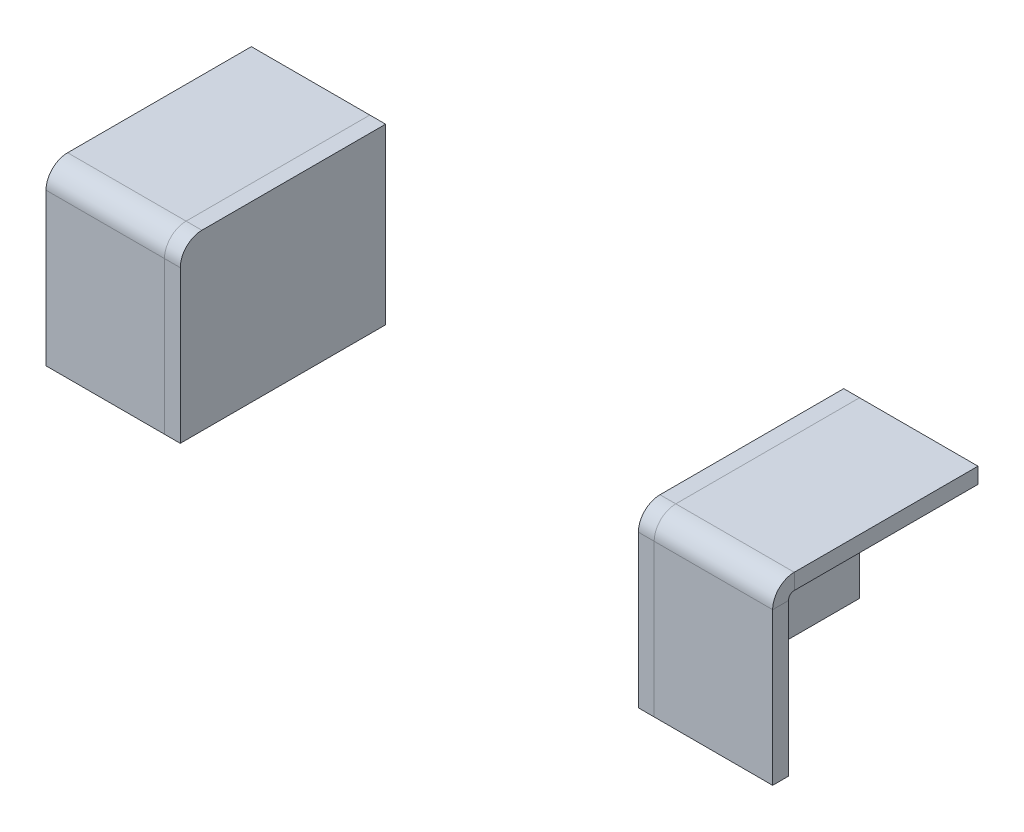
SolidWorks part; units mm, degrees
note: The reader was unsure of these and kept them because the rebuilt part matched: flange length of "Edge-Flange1".
ref_plane "Front Plane" through (0, 0, 0) normal (0, 0, 1) x (1, 0, 0)
ref_plane "Top Plane" through (0, 0, 0) normal (0, 1, 0) x (1, 0, 0)
ref_plane "Right Plane" through (0, 0, 0) normal (1, 0, 0) x (0, 0, -1)
sketch "Sketch1" plane through (0, 0, 0) normal (0, 1, 0) x (1, 0, 0)
  line L1 (-7.5, -13) -> (7.5, -13)
  line L2 (-7.5, -13) -> (-7.5, 13)
  line L3 (-7.5, 13) -> (7.5, 13)
  line L4 (7.5, -13) -> (7.5, 13)
  line L5 (-7.5, -13) -> (7.5, 13) construction
  line L6 (-7.5, 13) -> (7.5, -13) construction
  point P0 (0, 0)
  dimension "D1" = 26
  dimension "D2" = 15
base flange "Base-Flange1" sketch "Sketch1" thickness 2 reverse thickness direction no parameters "D1"=0.7366
edge flange "Edge-Flange1" sketch "Sketch8" flange angle 90 flange length 20 flange position material inside bend radius 0.7366 thickness 2 relief rectangular parameters "D6"=10
sketch "Sketch8" plane through (0, -2, 13) normal (0, 0, 1) x (-1, 0, 0)
  line L0 (7.5, 0) -> (-7.5, 0) construction
  line L1 (7.5, 0) -> (-7.5, 0)
  line L2 (-7.5, 0) -> (-7.5, 20)
  line L3 (-7.5, 20) -> (7.5, 20)
  line L4 (7.5, 20) -> (7.5, 0)
bend "EdgeBend1" bend radius 0.7366 bend angle 90 parameters "D5"=1
sketch "Sketch9" plane through (7.5, 0, 0) normal (1, 0, 0) x (0, 0, -1)
  line L0 (-13, -22) -> (-13, -2.7366) construction
  line L1 (-10.2634, 0) -> (13, 0) construction
  line L2 (-13, -22) -> (-13, -2.7366)
  line L3 (-10.2634, 0) -> (13, 0)
  line L4 (-13, -22) -> (13, -22)
  line L5 (13, -22) -> (13, 0)
  arc A0 (-10.2634, 0) -> (-13, -2.7366) centre (-10.2634, -2.7366) ccw construction
  arc A1 (-10.2634, 0) -> (-13, -2.7366) centre (-10.2634, -2.7366) ccw
base flange "Base-Flange2" sketch "Sketch9" thickness 2 reverse thickness direction yes parameters "D1"=0.7366
ref_plane "Plane1" through (38.5, 0, 0) normal (-1, 0, 0) x (0, 0, 1)
mirror "Mirror1" about plane through (38.5, 0, 0) normal (-1, 0, 0) of bodies 102 103
bend "DerivedBend1" bend radius 0.7366 bend angle 90 parameters "D5"=1
sketch "Bend-Lines1" [suppressed] plane through (0, 0, 0) normal (0, 1, 0) x (1, 0, 0)
sketch "Bounding-Box1" [suppressed] plane through (0, 0, 0) normal (0, 1, 0) x (1, 0, 0)
sheet metal parameters "Sheet-Metal1" thickness 2 parameters "D1"=0.7366
flat pattern "Flat-Pattern1" [suppressed]
sketch "Bend-Lines2" plane through (0, 0, 0) normal (0, 1, 0) x (1, 0, 0)
sketch3d "Bounding-Box2" [suppressed]
  line L0 (-46, 13, 0) -> (46, 13, 0) construction
  line L1 (-46, -13, 0) -> (46, -13, 0) construction
  line L2 (-46, 13, 0) -> (-46, -13, 0) construction
  line L3 (46, 13, 0) -> (46, -13, 0) construction
sheet metal parameters "Sheet-Metal2" thickness 2 parameters "D1"=0.7366
flat pattern "Flat-Pattern1"
sketch "Bend-Lines2" plane through (0, 0, 0) normal (0, 1, 0) x (1, 0, 0)
  line L0 (-7.5, -10.4634) -> (7.5, -10.4634) construction
  line L1 (-7.5, -10.4634) -> (7.5, -10.4634) construction
sketch3d "Bounding-Box2" [suppressed]
  line L0 (-7.5, -29.9268, 0) -> (-7.5, 13, 0) construction
  line L1 (7.5, -29.9268, 0) -> (7.5, 13, 0) construction
  line L2 (-7.5, -29.9268, 0) -> (7.5, -29.9268, 0) construction
  line L3 (-7.5, 13, 0) -> (7.5, 13, 0) construction
bend of the flat pattern "Flatten-<EdgeBend1>1"
sheet metal parameters "Sheet-Metal3" thickness 2 parameters "D1"=0.7366
flat pattern "Flat-Pattern3"
sketch "Bend-Lines3" plane through (0, 0, 0) normal (0, 1, 0) x (1, 0, 0)
sketch3d "Bounding-Box3" [suppressed]
  line L0 (2.7366, -19.2634, 0) -> (-23.2634, -19.2634, 0) construction
  line L1 (2.7366, 2.7366, 0) -> (-23.2634, 2.7366, 0) construction
  line L2 (2.7366, -19.2634, 0) -> (2.7366, 2.7366, 0) construction
  line L3 (-23.2634, -19.2634, 0) -> (-23.2634, 2.7366, 0) construction
sheet metal parameters "Sheet-Metal4" thickness 2 parameters "D1"=0.7366
flat pattern "Flat-Pattern4" [suppressed]
sketch "Bend-Lines4" plane through (0, 0, 0) normal (0, 1, 0) x (1, 0, 0)
sketch "Bounding-Box4" [suppressed] plane through (0, 0, 0) normal (0, 1, 0) x (1, 0, 0)
bend of the flat pattern "Flatten-<DerivedBend1>1"
sheet metal parameters "Sheet-Metal5" thickness 2 parameters "D1"=0.7366
flat pattern "Flat-Pattern5"
sketch "Bend-Lines5" plane through (0, 0, 0) normal (0, 1, 0) x (1, 0, 0)
sketch "Bounding-Box5" [suppressed] plane through (0, 0, 0) normal (0, 1, 0) x (1, 0, 0)
